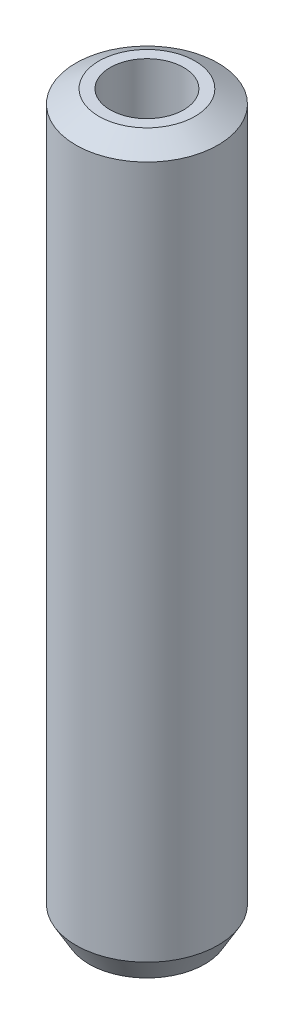
SolidWorks part; units mm, degrees
ref_plane "Front Plane" through (0, 0, 0) normal (0, 0, 1) x (1, 0, 0)
ref_plane "Top Plane" through (0, 0, 0) normal (0, 1, 0) x (1, 0, 0)
ref_plane "Right Plane" through (0, 0, 0) normal (1, 0, 0) x (0, 0, -1)
sketch "Sketch1" plane through (0, 0, 0) normal (0, 1, 0) x (1, 0, 0)
  circle A0 centre (0, 0) radius 22.5
  dimension "SHAFT_OD" = 45
extrude "Boss-Extrude1" add sketch "Sketch1" along normal blind 230.8083
sketch "Sketch2" plane through (0, 0, 0) normal (0, 1, 0) x (1, 0, 0)
  circle A0 centre (0, 0) radius 11.6331
  dimension "BORE_D" = 23.2662
extrude "Cut-Extrude1" cut sketch "Sketch2" along normal through all
chamfer "Chamfer1" distance 4.2162 angle 60 2 edges at (0, 230.8083, 22.5) (0, 0, 22.5) first distance on face at (0, 230.8083, 22.5) first distance on face at (0, 0, 11.6331)
